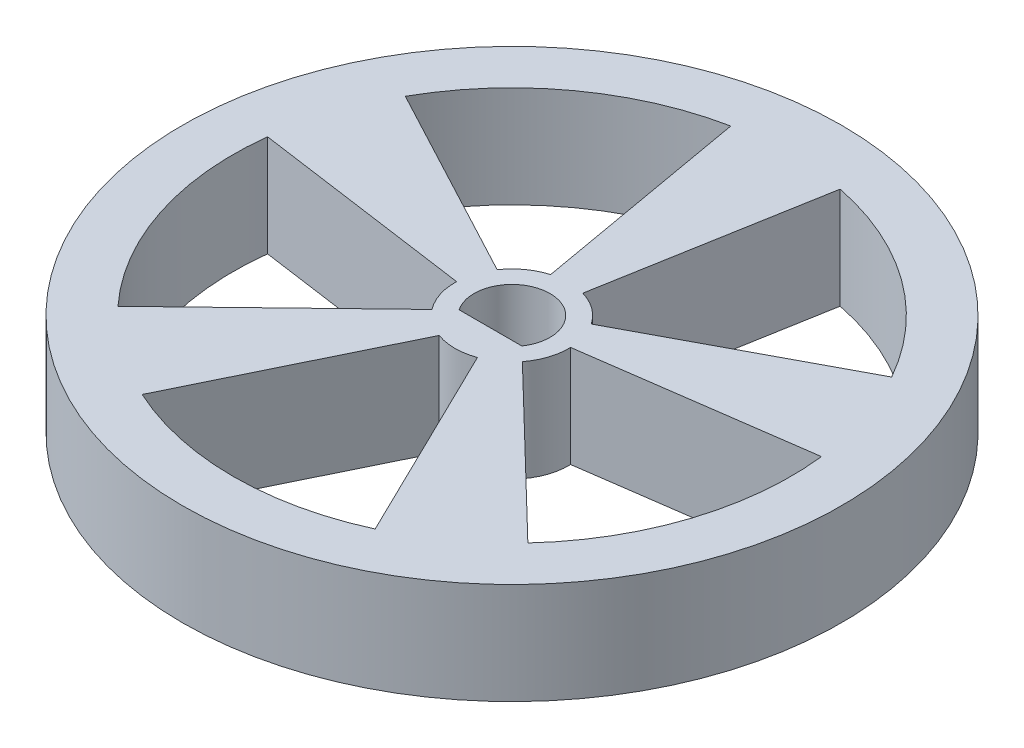
SolidWorks part; units mm, degrees
ref_plane "Front Plane" through (0, 0, 0) normal (0, 0, 1) x (1, 0, 0)
ref_plane "Top Plane" through (0, 0, 0) normal (0, 1, 0) x (1, 0, 0)
ref_plane "Right Plane" through (0, 0, 0) normal (1, 0, 0) x (0, 0, -1)
sketch "Sketch1" plane through (0, 0, 0) normal (0, 1, 0) x (1, 0, 0)
  line L0 (0, 1.5) -> (2.438, 1.5) construction
  line L1 (-1.2359, -0.85) -> (1.2359, -0.85)
  line L2 (0, 2.25) -> (0, 13) construction
  line L3 (-2.5037, 12.7566) -> (-0.635, 2.1585)
  line L4 (2.3787, 12.3726) -> (2.5037, 12.7566)
  line L5 (2.5037, 12.7566) -> (0.635, 2.1585)
  line L6 (11.3586, 6.3232) -> (1.8567, 1.2709)
  line L7 (12.906, 1.5608) -> (2.2491, 0.0631)
  line L8 (9.5237, -8.8487) -> (1.7825, -1.373)
  line L9 (5.4726, -11.792) -> (0.755, -2.1195)
  line L10 (-5.4726, -11.792) -> (-0.755, -2.1195)
  line L11 (-9.5237, -8.8487) -> (-1.7825, -1.373)
  line L12 (-12.906, 1.5608) -> (-2.2491, 0.0631)
  line L13 (-11.3586, 6.3232) -> (-1.8567, 1.2709)
  circle A0 centre (0, 0) radius 1.5
  circle A1 centre (0, 0) radius 2.25
  circle A2 centre (0, 0) radius 13
  circle A3 centre (0, 0) radius 11
  point P35 (0, 0)
  dimension "D1" = 2.35
  dimension "D2" = 10
  dimension "D3" = 10
  dimension "D4" = 0.635
  dimension "D5" = 0.635
  dimension "D6" = 5
extrude "Boss-Extrude1" add sketch "Sketch1" along normal blind 4 contours A1 A0 | L1 A0 | L5 A3 L3 A1 | A3 L5 A2 L3 | A3 L6 A2 L5 | A3 L7 A2 L6 | L7 A3 L6 A1 | A3 L8 A2 L7 | L9 A3 L8 A1 | A3 L9 A2 L8 | A3 L10 A2 L9 | A3 L11 A2 L10 | L11 A3 L10 A1 | A3 L13 A2 L12 | L13 A3 L12 A1 | A3 L3 A2 L13 | A3 L12 A2 L11 region at (0, 0, 1.1155) region at (0, 0, -11.9485) region at (-6.8517, 0, -9.4306) region at (0, 0, -7.3626) region at (6.8517, 0, -9.4306) region at (-11.3637, 0, -3.6923) region at (0, 0, -2.1864) region at (-7.0022, 0, -2.2752) region at (11.3637, 0, -3.6923) region at (-11.0863, 0, 3.6022) region at (7.0022, 0, -2.2752) region at (11.0863, 0, 3.6022) region at (-7.0231, 0, 9.6665) region at (-4.3276, 0, 5.9565) region at (0, 0, 11.6568) region at (7.0231, 0, 9.6665) region at (4.3276, 0, 5.9565)
extrude "Boss-Extrude2" add sketch "Sketch1<4>" along normal blind 0.5 contours A0
sketch "Sketch1<4>" plane through (0, 0, 0) normal (0, 1, 0) x (1, 0, 0) same geometry as "Sketch1"
